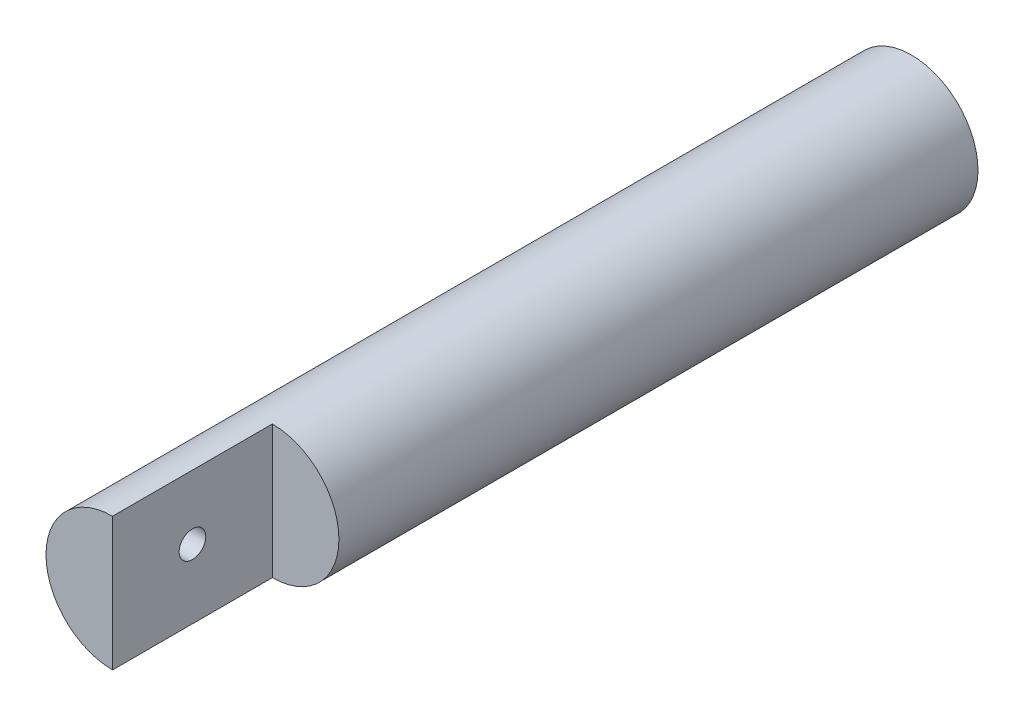
SolidWorks part; units mm, degrees
material "1345 Alloy"
ref_plane "Front Plane" through (0, 0, 0) normal (0, 0, 1) x (1, 0, 0)
ref_plane "Top Plane" through (0, 0, 0) normal (0, 1, 0) x (1, 0, 0)
ref_plane "Right Plane" through (0, 0, 0) normal (1, 0, 0) x (0, 0, -1)
sketch "Sketch2" plane through (0, 0, 0) normal (0, 0, 1) x (1, 0, 0)
  line L1 (0, 0) -> (-30, 0)
  line L2 (0, 0) -> (0, 30)
  line L3 (0, 30) -> (-30, 30)
  line L4 (-30, 0) -> (-30, 30)
  dimension "D1" = 30
  dimension "D2" = 30
extrude "Boss-Extrude2" add sketch "Sketch2" along normal blind 150
sketch "Sketch3" plane through (0, 0, 0) normal (1, 0, 0) x (0, 0, -1)
  line L0 (-150, 0) -> (-150, 30) construction
  line L1 (-150, 0) -> (0, 0) construction
  circle A0 centre (-135, 15) radius 2.5
  dimension "D1" = 5
  dimension "D3" = 15
  dimension "D2" = 15
extrude "Cut-Extrude1" cut sketch "Sketch3" against normal blind 30
sketch "Sketch4" plane through (0, 0, 150) normal (0, 0, 1) x (1, 0, 0)
  line L0 (-30, 30) -> (-30, 0) construction
  circle A0 centre (-15, 14.5516) radius 12.5
  dimension "D2" = 25
  dimension "D1" = 15
extrude "Cut-Extrude2" cut sketch "Sketch4" against normal blind 150 flip side to cut contours A0
sketch "Sketch5" plane through (0, 0, 0) normal (0, 0, -1) x (-1, 0, 0)
  circle A0 centre (15, 14.5516) radius 11.5
  dimension "D1" = 23
extrude "Cut-Extrude3" cut sketch "Sketch5" against normal blind 110
sketch "Sketch7" plane through (0, 0, 150) normal (0, 0, 1) x (1, 0, 0)
  line L1 (-15, 27.0516) -> (-2.5, 27.0516)
  line L2 (-15, 27.0516) -> (-15, 2.0516)
  line L3 (-15, 2.0516) -> (-2.5, 2.0516)
  line L4 (-2.5, 27.0516) -> (-2.5, 2.0516)
  circle A0 centre (-15, 14.5516) radius 12.5 construction
  dimension "D1" = 25
  dimension "D2" = 12.5
extrude "Cut-Extrude4" cut sketch "Sketch7" against normal blind 30
ref_axis "Axis1" through (-38.1297, 15, 135) along (1, 0, 0)
